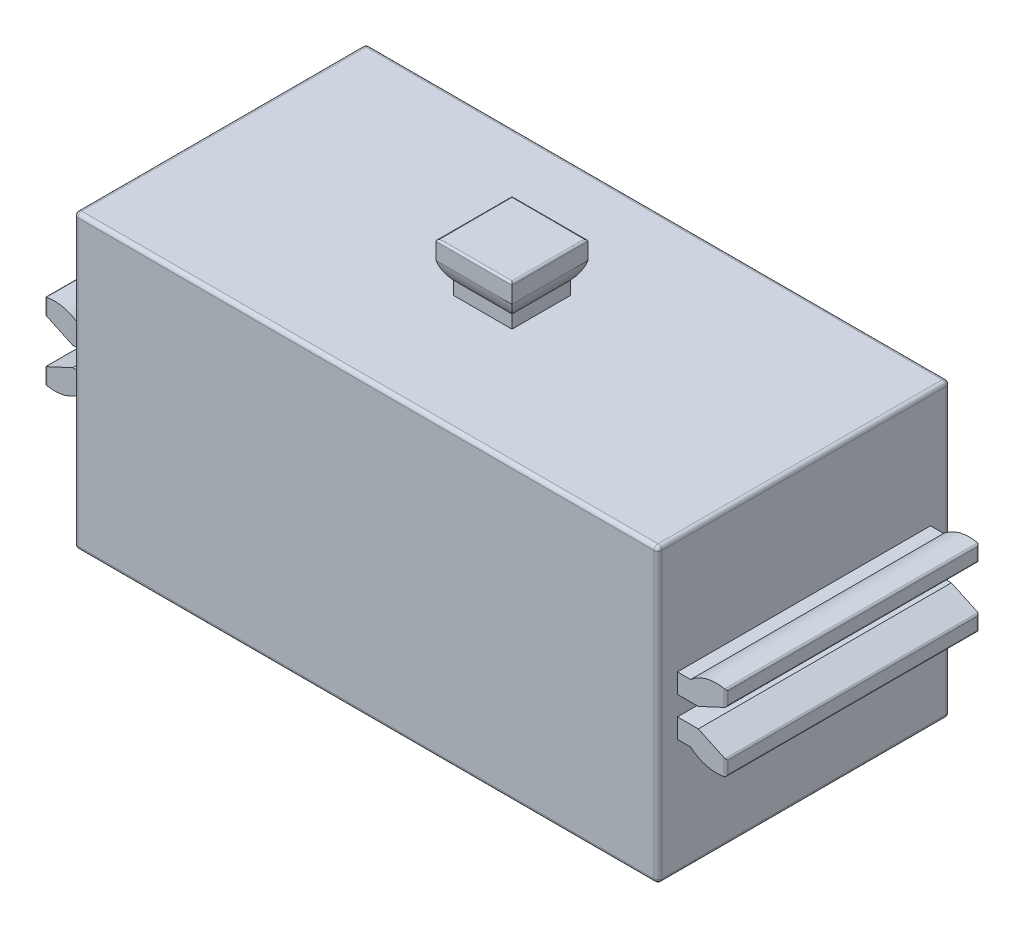
SolidWorks part; units mm, degrees
ref_plane "前视基准面" through (0, 0, 0) normal (0, 0, 1) x (1, 0, 0)
ref_plane "上视基准面" through (0, 0, 0) normal (0, 1, 0) x (1, 0, 0)
ref_plane "右视基准面" through (0, 0, 0) normal (1, 0, 0) x (0, 0, -1)
sketch "草图1" plane through (0, 0, 0) normal (0, 0, 1) x (1, 0, 0)
  line L1 (-15, -7.5) -> (15, -7.5)
  line L2 (-15, -7.5) -> (-15, 7.5)
  line L3 (-15, 7.5) -> (15, 7.5)
  line L4 (15, -7.5) -> (15, 7.5)
extrude "凸台-拉伸1" add sketch "草图1" along normal blind 7.5 and the other way blind 7.5
sketch "草图2" plane through (0, 0, 7.5) normal (0, 0, 1) x (1, 0, 0)
  line L0 (-15, 7.5) -> (-15, -7.5) construction
  line L1 (-15.6771, 1.5) -> (-15, 1.5)
  line L2 (-17.5, 1.9365) -> (-17.5, 1.1658)
  line L3 (-15.6771, -1.5) -> (-15, -1.5)
  line L4 (-15, 1.5) -> (-15, 0.5)
  line L5 (-16.0723, 0.5) -> (-17.5, 1.1658)
  line L6 (-16.0723, -0.5) -> (-17.5, -1.1658)
  line L7 (-17.5, -1.1658) -> (-17.5, -1.9365)
  line L8 (-15, -0.5) -> (-16.0723, -0.5)
  line L9 (0, 8.7474) -> (0, -8.6547) construction
  line L10 (-15, 0.5) -> (-16.0723, 0.5)
  line L11 (-15, -0.5) -> (-15, -1.5)
  line L12 (15, -0.5) -> (15, -1.5)
  line L13 (15, 0.5) -> (16.0723, 0.5)
  line L14 (15, -0.5) -> (16.0723, -0.5)
  line L15 (17.5, -1.1658) -> (17.5, -1.9365)
  line L16 (16.0723, -0.5) -> (17.5, -1.1658)
  line L17 (16.0723, 0.5) -> (17.5, 1.1658)
  line L18 (15, 1.5) -> (15, 0.5)
  line L19 (15.6771, -1.5) -> (15, -1.5)
  line L20 (17.5, 1.9365) -> (17.5, 1.1658)
  line L21 (15.6771, 1.5) -> (15, 1.5)
  arc A0 (-15.6771, 1.5) -> (-17.5, 1.9365) centre (-17, 0) ccw
  arc A1 (-17.5, -1.9365) -> (-15.6771, -1.5) centre (-17, 0) ccw
  arc A2 (17.5, -1.9365) -> (15.6771, -1.5) centre (17, 0) cw
  arc A3 (15.6771, 1.5) -> (17.5, 1.9365) centre (17, 0) cw
extrude "凸台-拉伸2" add sketch "草图2" against normal blind 13 from offset 1 offset against normal yes
sketch "草图3" plane through (0, 7.5, 0) normal (0, 1, 0) x (-1, 0, 0)
  line L1 (1.5, -1.5) -> (-1.5, -1.5)
  line L2 (1.5, -1.5) -> (1.5, 1.5)
  line L3 (1.5, 1.5) -> (-1.5, 1.5)
  line L4 (-1.5, -1.5) -> (-1.5, 1.5)
extrude "凸台-拉伸3" add sketch "草图3" along normal blind 1
sketch "草图4" plane through (0, 0, 0) normal (0, 0, 1) x (1, 0, 0)
  line L0 (-1.95, 10) -> (1.95, 10)
  line L1 (-1.95, 10) -> (-1.95, 9.0556)
  line L2 (1.95, 10) -> (1.95, 9.0556)
  line L5 (-1.5, 8.1771) -> (1.5, 8.1771)
  line L6 (1.5, 8.5) -> (1.5, 7.5) construction
  arc A0 (1.5, 8.1771) -> (1.95, 9.0556) centre (0, 9.5) ccw
  arc A2 (-1.95, 9.0556) -> (-1.5, 8.1771) centre (0, 9.5) ccw
extrude "凸台-拉伸4" add sketch "草图4" along normal blind 2 and the other way blind 3
sketch "草图5" plane through (1.95, 0, 0) normal (1, 0, 0) x (0, 0, -1)
  line L1 (-1.95, 10) -> (-1.95, 9.0556)
  line L2 (-2, 10) -> (-1.95, 10)
  line L3 (-2, 10) -> (-2, 8.1771)
  line L4 (-2, 8.1771) -> (-1.5, 8.1771)
  line L5 (3, 10) -> (3, 8.1771)
  line L6 (1.95, 10) -> (1.95, 9.0556)
  line L7 (1.95, 10) -> (3, 10)
  line L8 (1.5, 8.1771) -> (3, 8.1771)
  arc A0 (1.5, 8.1771) -> (1.95, 9.0556) centre (0, 9.5) ccw
  arc A1 (-1.95, 9.0556) -> (-1.5, 8.1771) centre (0, 9.5) ccw
extrude "切除-拉伸1" cut sketch "草图5" against normal up to next
fillet "圆角1" radius 0.1 20 edges at (1.95, 10, 0) (0, 10, 1.95) (-1.95, 10, 0) (0, 10, -1.95) (-17.5, -1.9365, 0) (-17.5, -1.5511, -6.5) (-17.5, -1.1658, 0) (-17.5, -1.5511, 6.5) (-17.5, 1.1658, 0) (-17.5, 1.5511, -6.5) (-17.5, 1.9365, 0) (-17.5, 1.5511, 6.5) (17.5, -1.1658, 0) (17.5, -1.5511, -6.5) (17.5, -1.9365, 0) (17.5, -1.5511, 6.5) (17.5, 1.9365, 0) (17.5, 1.5511, -6.5) (17.5, 1.1658, 0) (17.5, 1.5511, 6.5)
fillet "圆角2" radius 0.2 12 edges at (0, -7.5, -7.5) (15, 0, -7.5) (0, 7.5, -7.5) (-15, 0, -7.5) (0, 7.5, 7.5) (15, 0, 7.5) (0, -7.5, 7.5) (-15, 0, 7.5) (-15, -7.5, 0) (-15, 7.5, 0) (15, 7.5, 0) (15, -7.5, 0)
sketch "草图6" plane through (0, -7.5, 0) normal (0, -1, 0) x (1, 0, 0)
  line L0 (0, 0) -> (-2.8, 0) construction
  circle A0 centre (-2.8, 0) radius 1.7
  dimension "D2" = 3.4
  dimension "D1" = 2.8
extrude "切除-拉伸2" cut sketch "草图6" against normal blind 1
mirror "镜向2" about plane through (0, 0, 0) normal (1, 0, 0) of "切除-拉伸2"
